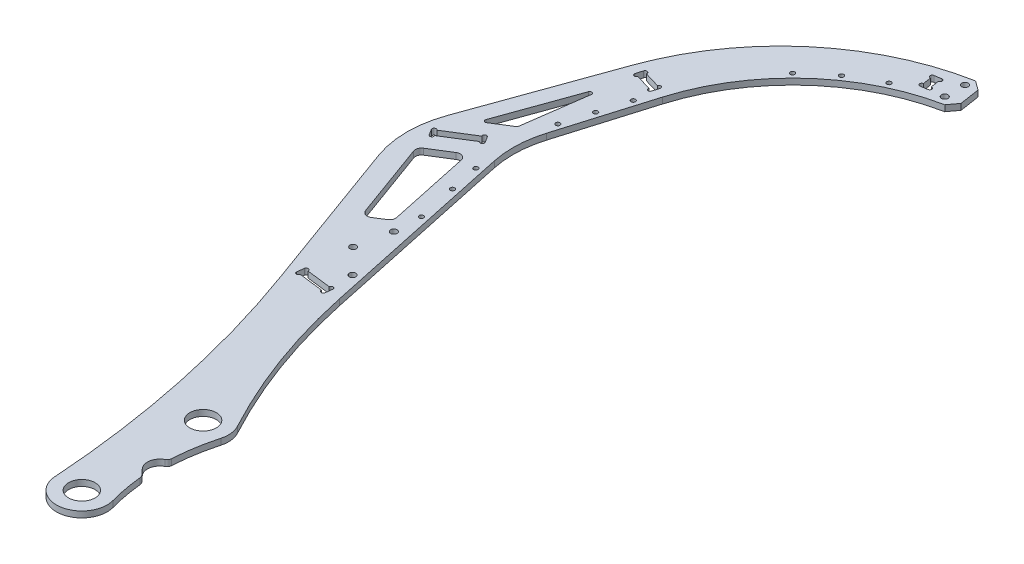
SolidWorks part; units mm, degrees
material "碳板"
ref_plane "前视基准面" through (0, 0, 0) normal (0, 0, 1) x (1, 0, 0)
ref_plane "上视基准面" through (0, 0, 0) normal (0, 1, 0) x (1, 0, 0)
ref_plane "右视基准面" through (0, 0, 0) normal (1, 0, 0) x (0, 0, -1)
sketch "草图1" plane through (0, 0, 0) normal (0, 1, 0) x (1, 0, 0)
  line L0 (0, 0) -> (0, -60)
  line L1 (0, 0) -> (-41.7329, 195.5975)
  line L2 (-41.7329, 195.5975) -> (-13.083, 291.4055)
  line L3 (196.3372, 468.2646) -> (235.872, 211.288) construction
  line L4 (39.173, 371.8311) -> (47.0553, 320.5961) construction
  line L5 (97.5, 453.0589) -> (97.5, 190) construction
  line L6 (191.3953, 467.5044) -> (230.9302, 210.5277)
  line L7 (43.7907, 374.6988) -> (52.618, 317.3209)
  line L8 (97.5, 190) -> (97.5, 602.4977) construction
  arc A0 (196.3372, 468.2646) -> (39.173, 371.8311) centre (97.5, 453.0589) ccw construction
  arc A1 (47.0553, 320.5961) -> (235.872, 211.288) centre (97.5, 190) ccw construction
  arc A2 (52.618, 317.3209) -> (230.9302, 210.5277) centre (97.5, 190) ccw
  arc A3 (191.3953, 467.5044) -> (43.7907, 374.6988) centre (97.5, 453.0589) ccw
  point P11 (97.5, 50)
  dimension "D6" = 140
  dimension "D7" = 100
  dimension "D9" = 170
  dimension "D1" = 60
  dimension "D2" = 5
  dimension "D3" = 200
  dimension "D4" = 190
  dimension "D5" = 100
  dimension "D8" = 260
  dimension "D10" = 97.5
sketch "草图3" plane through (0, 0, 0) normal (0, 1, 0) x (1, 0, 0)
  line L2 (0, 128.9154) -> (0, -114.3284) construction
  line L3 (-96.7061, 0) -> (305.45, 0) construction
  line L4 (0, 0) -> (-41.7329, 195.5975) construction
  line L5 (0, 0) -> (-41.7329, 195.5975) construction
  line L6 (-18.2954, 85.7484) -> (-41.7329, 195.5975)
  line L7 (-41.7329, 195.5975) -> (-13.083, 291.4055) construction
  line L8 (-41.7329, 195.5975) -> (-24.8302, 252.1217)
  line L9 (52.3139, 319.2976) -> (81.8409, 323.8403) construction
  line L10 (-45.908, 258.4246) -> (-76.2901, 173.9446)
  line L11 (-76.2901, 173.9446) -> (-14.5089, 4.202)
  line L12 (52.3139, 319.2976) -> (49.5769, 337.0883)
  line L13 (43.7907, 374.6988) -> (52.618, 317.3209) construction
  line L14 (43.7907, 374.6988) -> (52.618, 317.3209) construction
  line L15 (49.5769, 337.0883) -> (85.4286, 342.604) construction
  line L16 (-45.908, 258.4246) -> (-24.8302, 252.1217) construction
  circle A0 centre (0, -60) radius 6.55
  circle A1 centre (0, 0) radius 6.55
  arc A4 (12.096, -3.3452) -> (-12.096, -3.3452) centre (0, 0) ccw
  arc A5 (-12.096, -56.6548) -> (12.096, -56.6548) centre (0, -60) ccw
  arc A6 (-12.096, -3.3452) -> (-12.096, -56.6548) centre (-108.4781, -30) cw
  arc A7 (12.096, -3.3452) -> (12.096, -56.6548) centre (108.4781, -30) ccw
  circle A9 centre (0, 0) radius 12.55 construction
  circle A10 centre (0, -60) radius 12.55 construction
  arc A11 (52.618, 317.3209) -> (230.9302, 210.5277) centre (97.5, 190) ccw construction
  arc A12 (11.0463, 5.9567) -> (-18.2954, 85.7484) centre (275.1008, 148.3477) cw
  circle A14 centre (-108.4781, -30) radius 100 construction
  arc A15 (-14.5089, 4.202) -> (-12.096, -3.3452) centre (-108.4781, -30) cw
  arc A16 (52.618, 317.3209) -> (230.9302, 210.5277) centre (97.5, 190) ccw construction
  arc A17 (-24.8302, 252.1217) -> (52.3139, 319.2976) centre (66.8673, 224.701) cw
  arc A18 (-45.908, 258.4246) -> (49.5769, 337.0883) centre (67.9803, 217.4662) cw
  point P7 (12.5, -60)
  point P20 (12.5, 0)
  dimension "D1" = 13.1
  dimension "D2" = 13.1
  dimension "D3" = 6
  dimension "D4" = 100
  dimension "D5" = 300
  dimension "D8" = 18
  dimension "D6" = 2
  dimension "D7" = 70
  dimension "D9" = 22
extrude "凸台-拉伸1" add sketch "草图3" along normal mid plane 3 contours L11 A15 A4 A12 L6 L8 L10 | A7 A4 A6 A5 A1 A0 region at (-9.8809, 0, -43.5519) region at (0, 0, 30)
sketch "草图7" plane through (0, 1.5, 0) normal (0, 1, 0) x (1, 0, 0)
  line L0 (0, 0) -> (0, -60) construction
  line L1 (0, -60) -> (5.2094, -30.4558) construction
  line L2 (8.6427, -24.2646) -> (-8.6427, -24.2646) construction
  line L3 (-8.9098, -39.2813) -> (8.9098, -39.2813) construction
  line L4 (5.2094, -30.4558) -> (-19.4375, -30.4558) construction
  line L5 (4.4975, -34.4935) -> (8.9098, -39.2813)
  circle A0 centre (5.2094, -30.4558) radius 4.1
  circle A1 centre (0, -60) radius 25.9 construction
  circle A2 centre (0, -60) radius 34.1 construction
  arc A3 (5.9214, -26.4181) -> (8.6427, -24.2646) centre (6.3246, -24.1314) ccw
  arc A4 (12.096, -3.3452) -> (12.096, -56.6548) centre (108.4781, -30) ccw construction
  arc A5 (12.096, -3.3452) -> (12.096, -56.6548) centre (108.4781, -30) ccw
  arc A6 (4.4975, -34.4935) -> (8.9098, -39.2813) centre (3.5654, -39.7794) cw
  arc A7 (-8.6427, -24.2646) -> (-9.4191, -26.6379) centre (-12.0585, -24.4608) cw
  arc A8 (-12.096, -56.6548) -> (-14.5089, 4.202) centre (-108.4781, -30) ccw construction
  arc A9 (-9.4191, -26.6379) -> (-10.1033, -33.2441) centre (-4.7906, -30.4558) ccw
  arc A10 (-10.1033, -33.2441) -> (-8.9098, -39.2813) centre (-19.6915, -38.2762) cw
  arc A11 (-12.096, -56.6548) -> (-14.5089, 4.202) centre (-108.4781, -30) ccw
  arc M21 (-14.5089, 4.202) -> (-12.096, -56.6548) centre (-108.4781, -30) cw
  arc M23 (12.096, -56.6548) -> (12.096, -3.3452) centre (108.4781, -30) cw
  dimension "D3" = 8.2
  dimension "D4" = 6
  dimension "D5" = 10
  dimension "D1" = 30
  dimension "D2" = 10
extrude "切除-拉伸3" cut sketch "草图7" against normal through all contours A0 A6 A5 A3 | A0 | A3 A0 M23 | A0 A6 M23 | A6 L5 region at (5.0111, 1.5, 30.4566) region at (7.6822, 1.5, 35.1992) region at (7.9334, 1.5, 26.511)
extrude "凸台-拉伸2" add sketch "草图7<3>" against normal up to surface (3 mm away) contours A9 A10 A7 M21 region at (-9.3929, 1.5, 30.8168) up to face at (0, -1.5, 66.55)
sketch "草图7<3>" plane through (0, 1.5, 0) normal (0, 1, 0) x (1, 0, 0) same geometry as "草图7"
chamfer "倒角1" distance 4 angle 45 2 edges at (49.5769, 0, -337.0883) (52.3139, 0, -319.2976)
sketch "草图8" plane through (0, 1.5, 0) normal (0, 1, 0) x (1, 0, 0)
  line L0 (38.9851, 300.7114) -> (27.3795, 376.1481) construction
  line L1 (51.7057, 323.2511) -> (50.1851, 333.1348) construction
  line L2 (0, 491.3509) -> (0, -203.5578) construction
  line L3 (-514.9295, 0) -> (416.4369, 0) construction
  line L4 (36.3536, 328.9962) -> (37.5853, 320.9904)
  line L5 (36.3536, 328.9962) -> (32.9931, 328.4792)
  line L6 (37.5853, 320.9904) -> (34.2248, 320.4734)
  line L7 (32.9931, 328.4792) -> (34.2248, 320.4734)
  line L8 (36.3536, 328.9962) -> (34.2248, 320.4734) construction
  line L9 (37.5853, 320.9904) -> (32.9931, 328.4792) construction
  line L10 (44.7874, 322.0898) -> (60.2067, 322.0898) construction
  line L11 (-55.233, 261.2131) -> (-176.9888, 297.6222) construction
  line L16 (-41.7329, 195.5975) -> (-24.8302, 252.1217) construction
  line L17 (-40.7264, 258.6495) -> (-29.1336, 255.1829)
  line L19 (-40.7264, 258.6495) -> (-41.7005, 255.392)
  line L20 (-29.1336, 255.1829) -> (-30.1077, 251.9254)
  line L21 (-41.7005, 255.392) -> (-30.1077, 251.9254)
  line L22 (-40.7264, 258.6495) -> (-30.1077, 251.9254) construction
  line L23 (-29.1336, 255.1829) -> (-41.7005, 255.392) construction
  line L24 (-41.7329, 195.5975) -> (-76.2901, 173.9446) construction
  line L25 (-68.1422, 181.0561) -> (-51.1095, 191.7284)
  line L26 (-68.1422, 181.0561) -> (-66.3369, 178.175)
  line L27 (-51.1095, 191.7284) -> (-49.3042, 188.8473)
  line L28 (-66.3369, 178.175) -> (-49.3042, 188.8473)
  line L29 (-68.1422, 181.0561) -> (-49.3042, 188.8473) construction
  line L30 (-51.1095, 191.7284) -> (-66.3369, 178.175) construction
  line L31 (-18.2954, 85.7484) -> (-45.3995, 89.0733) construction
  line L32 (-76.2901, 173.9446) -> (-14.5089, 4.202) construction
  line L33 (-40.0239, 90.1266) -> (-24.0437, 88.1663)
  line L34 (-40.0239, 90.1266) -> (-40.4379, 86.7519)
  line L35 (-24.0437, 88.1663) -> (-24.4577, 84.7916)
  line L36 (-40.4379, 86.7519) -> (-24.4577, 84.7916)
  line L37 (-40.0239, 90.1266) -> (-24.4577, 84.7916) construction
  line L38 (-24.0437, 88.1663) -> (-40.4379, 86.7519) construction
  circle A0 centre (37.4332, 321.9788) radius 1
  circle A1 centre (36.5057, 328.0078) radius 1
  circle A2 centre (33.1452, 327.4909) radius 1
  circle A3 centre (34.0727, 321.4618) radius 1
  circle A4 centre (44.7874, 332.0898) radius 1.6
  circle A5 centre (44.7874, 322.0898) radius 1.6
  circle A6 centre (-39.7683, 258.363) radius 1
  circle A7 centre (-40.7424, 255.1055) radius 1
  circle A8 centre (-30.0917, 255.4694) radius 1
  circle A9 centre (-31.0658, 252.2119) radius 1
  circle A10 centre (-67.2948, 181.5871) radius 1
  circle A11 centre (-65.4895, 178.7059) radius 1
  circle A12 centre (-51.9569, 191.1975) radius 1
  circle A13 centre (-50.1516, 188.3163) radius 1
  circle A14 centre (-25.0363, 88.288) radius 1
  circle A15 centre (-25.4503, 84.9133) radius 1
  circle A16 centre (-39.0314, 90.0049) radius 1
  circle A17 centre (-39.4454, 86.6302) radius 1
  point P12 (35.2892, 324.7348)
  point P38 (-35.417, 255.2875)
  point P45 (-58.7232, 184.9517)
  point P69 (-32.2408, 87.4591)
  dimension "D2" = 2
  dimension "D4" = 3.2
  dimension "D13" = 2
  dimension "D17" = 2
  dimension "D21" = 2
  dimension "D1" = 3.4
  dimension "D3" = 16
  dimension "D5" = 10
  dimension "D6" = 3.5
  dimension "D7" = 3.5
  dimension "D8" = 8.1
  dimension "D9" = 4
  dimension "D10" = 3.4
  dimension "D11" = 12.1
  dimension "D12" = 5
  dimension "D14" = 3.4
  dimension "D15" = 20.1
  dimension "D16" = 10
  dimension "D18" = 3.4
  dimension "D19" = 16.1
  dimension "D20" = 6
extrude "切除-拉伸6" cut sketch "草图8" against normal through all contours L33 L35 L36 L34 | A16 | A17 | A14 | A15 | L27 L28 L26 L25 | A12 | A13 | A10 | A11 | L19 L21 L20 L17 | A6 | A8 | A9 | A7 | A4 | A5 | L4 L6 L7 L5 | A1 | A2 | A3 | A0
sketch "草图9" plane through (0, 1.5, 0) normal (0, 1, 0) x (1, 0, 0)
  line L0 (66.8673, 224.701) -> (25.1508, 314.1623) construction
  line L1 (10.2498, 305.5592) -> (66.8673, 224.701) construction
  line L2 (-2.931, 294.4992) -> (66.8673, 224.701) construction
  line L3 (97.5, 453.0589) -> (97.5, 190) construction
  line L4 (-18.2954, 85.7484) -> (-41.7329, 195.5975) construction
  line L6 (-44.6071, 196.457) -> (-15.9573, 292.265)
  line L7 (-44.6071, 196.457) -> (-15.9573, 292.265) construction
  line L8 (-33.6468, 128) -> (-25.2549, 99.1976) construction
  line L9 (-2.934, -0.626) -> (-44.6668, 194.9715)
  line L10 (-2.934, -0.626) -> (-44.6668, 194.9715) construction
  line L12 (-29.4509, 113.5988) -> (-37.1315, 111.361) construction
  circle A0 centre (-30.5695, 243.4003) radius 1.1
  circle A1 centre (25.1508, 314.1623) radius 1.1
  arc A2 (47.705, 321.5328) -> (-27.7045, 252.9811) centre (66.8673, 224.701) ccw
  arc A3 (47.705, 321.5328) -> (-27.7045, 252.9811) centre (66.8673, 224.701) ccw construction
  circle A4 centre (10.2498, 305.5592) radius 1.1
  circle A5 centre (-34.8669, 229.0291) radius 1.1
  circle A6 centre (-2.931, 294.4992) radius 1.1
  circle A7 centre (-39.1644, 214.6579) radius 1.1
  circle A8 centre (-40.4936, 175.4117) radius 1.1
  circle A9 centre (-37.3636, 160.7419) radius 1.1
  circle A10 centre (-33.1903, 141.1822) radius 1.1
  circle A11 centre (-33.6468, 128) radius 1.6
  circle A12 centre (-25.2549, 99.1976) radius 1.6
  circle A13 centre (-37.1315, 111.361) radius 1.6
  dimension "D2" = 2.2
  dimension "D3" = 25
  dimension "D7" = 10
  dimension "D11" = 20
  dimension "D14" = 3.2
  dimension "D16" = 8
  dimension "D4" = 10
  dimension "D5" = 10
  dimension "D8" = 15
  dimension "D9" = 15
  dimension "D12" = 15
  dimension "D13" = 20
  dimension "D15" = 4
  dimension "D17" = 30
  dimension "D18" = 128
  dimension "D19" = 4.2
  dimension "D1" = 3
  dimension "D6" = 3
  dimension "D10" = 3
extrude "切除-拉伸7" cut sketch "草图9" against normal through all
sketch "草图10" plane through (0, 1.5, 0) normal (0, 1, 0) x (1, 0, 0)
  line L0 (-42.1973, 245.1031) -> (-59.8369, 196.0547)
  line L1 (-59.8369, 196.0547) -> (-47.9733, 203.4882)
  line L2 (-47.9733, 203.4882) -> (-42.1973, 245.1031)
  line L3 (-64.127, 169.7649) -> (-48.5313, 179.5369)
  line L5 (-48.3882, 126.5227) -> (-64.127, 169.7649)
  line L6 (-76.2901, 173.9446) -> (-14.5089, 4.202) construction
  line L7 (-48.3882, 126.5227) -> (-38.5371, 132.6952)
  line L8 (-38.5371, 132.6952) -> (-48.5313, 179.5369)
  line L9 (-18.2954, 85.7484) -> (-41.7329, 195.5975) construction
  line L10 (-76.2901, 173.9446) -> (-41.7329, 195.5975) construction
  line L11 (-45.908, 258.4246) -> (-76.2901, 173.9446) construction
  line L12 (-39.7843, 254.819) -> (-32.0239, 252.4984) construction
  dimension "D1" = 8
  dimension "D2" = 10
  dimension "D3" = 10
  dimension "D4" = 10
  dimension "D5" = 10
  dimension "D6" = 45
  dimension "D7" = 10
  dimension "D8" = 14
extrude "切除-拉伸8" cut sketch "草图10" against normal through all
fillet "圆角4" radius 50 2 edges at (-41.7329, 0, -195.5975) (-76.2901, 0, -173.9446)
fillet "圆角5" radius 3 6 edges at (-48.5313, 0, -179.5369) (-38.5371, 0, -132.6952) (-48.3882, 0, -126.5227) (-64.127, 0, -169.7649) (8.9098, 0, 39.2813) (4.4975, 0, 34.4935)
fillet "圆角6" radius 1 3 edges at (-59.8369, 0, -196.0547) (-47.9733, 0, -203.4882) (-42.1973, 0, -245.1031)
sketch "草图11" plane through (0, 1.5, 0) normal (0, 1, 0) x (1, 0, 0)
  line L0 (-70.1029, 156.9455) -> (-14.5089, 4.202) construction
  line L1 (5.0828, -35.1286) -> (8.2285, -38.542) construction
  line L4 (5.0828, -35.1286) -> (5.7604, -35.8639)
  line L6 (0, 60.9145) -> (0, -84.8123) construction
  line L9 (0, -60) -> (-21.6343, -60) construction
  line L10 (-42.3059, 80.5738) -> (-14.5089, 4.202)
  arc A0 (-12.55, -60) -> (-42.3059, 80.5738) centre (-524.5009, -94.9308) ccw
  arc A1 (5.0828, -35.1286) -> (3.8624, -34.3282) centre (2.8767, -37.1616) ccw construction
  arc A2 (5.9214, -26.4181) -> (8.6427, -24.2646) centre (6.3246, -24.1314) ccw construction
  arc A3 (5.9214, -26.4181) -> (7.4133, -26.1823) centre (6.3246, -24.1314) ccw
  arc A4 (5.0828, -35.1286) -> (3.8624, -34.3282) centre (2.8767, -37.1616) ccw
  arc A5 (5.9214, -26.4181) -> (3.8624, -34.3282) centre (5.2094, -30.4558) ccw construction
  arc A6 (5.9214, -26.4181) -> (3.8624, -34.3282) centre (5.2094, -30.4558) ccw
  arc A9 (7.4133, -26.1823) -> (5.7604, -35.8639) centre (10.3214, -31.6607) ccw
  arc A10 (-12.096, -56.6548) -> (12.096, -56.6548) centre (0, -60) ccw construction
  arc A12 (-8.6427, -24.2646) -> (-14.5089, 4.202) centre (-108.4781, -30) ccw construction
  arc A13 (-8.6427, -24.2646) -> (-14.5089, 4.202) centre (-108.4781, -30) ccw
  arc A14 (-9.4191, -26.6379) -> (-8.6427, -24.2646) centre (-12.0585, -24.4608) ccw construction
  arc A15 (-9.4191, -26.6379) -> (-8.6427, -24.2646) centre (-12.0585, -24.4608) ccw
  arc A16 (-9.4191, -26.6379) -> (-10.1033, -33.2441) centre (-4.7906, -30.4558) ccw construction
  arc A17 (-9.4191, -26.6379) -> (-10.1033, -33.2441) centre (-4.7906, -30.4558) ccw
  arc A18 (-8.9098, -39.2813) -> (-10.1033, -33.2441) centre (-19.6915, -38.2762) ccw construction
  arc A19 (-8.9098, -39.2813) -> (-10.1033, -33.2441) centre (-19.6915, -38.2762) ccw
  arc A20 (-12.096, -56.6548) -> (-8.9098, -39.2813) centre (-108.4781, -30) ccw construction
  arc A21 (-12.096, -56.6548) -> (-8.9098, -39.2813) centre (-108.4781, -30) ccw
  arc A22 (-12.096, -56.6548) -> (-12.55, -60) centre (0, -60) ccw
  arc A23 (0, -72.55) -> (12.096, -56.6548) centre (0, -60) ccw
  dimension "D1" = 1
extrude "凸台-拉伸3" add sketch "草图11" against normal up to surface (3 mm away) contours A6 A4 | A22 A21 A19 A17 A15 A13 L10 A0 region at (3.3317, 1.5, 30.032) region at (-16.7758, 1.5, 6.9105) up to face at (-50.2701, -1.5, -212.582)
move or copy body "实体-移动/复制1" [suppressed] bodies to move or copy 111
